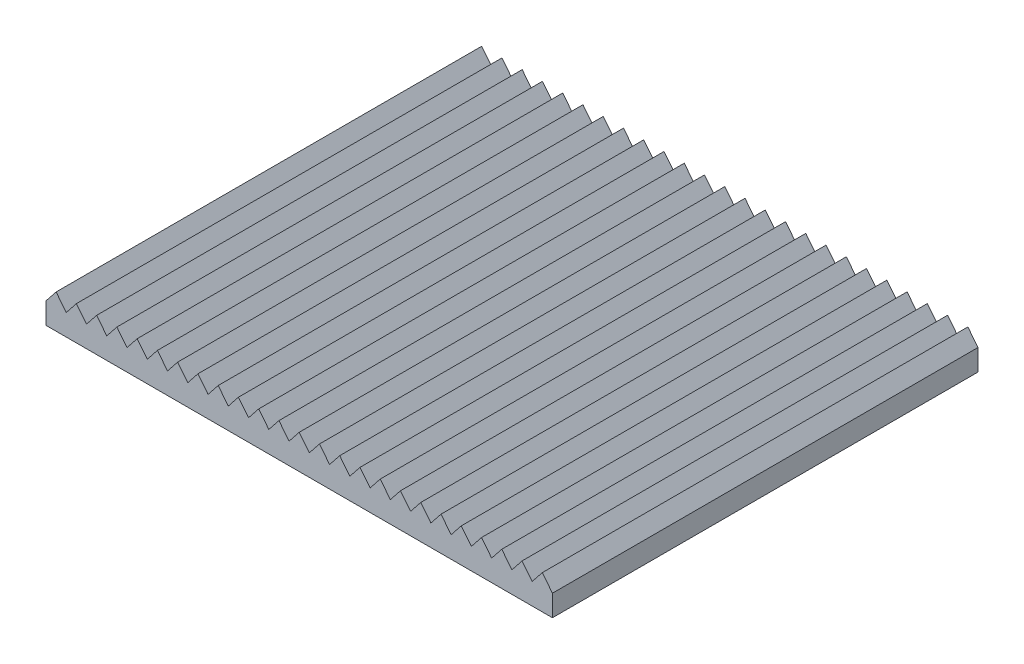
SolidWorks part; units mm, degrees
ref_plane "Front Plane" through (0, 0, 0) normal (0, 0, 1) x (1, 0, 0)
ref_plane "Top Plane" through (0, 0, 0) normal (0, 1, 0) x (1, 0, 0)
ref_plane "Right Plane" through (0, 0, 0) normal (1, 0, 0) x (0, 0, -1)
sketch "Sketch1" plane through (0, 0, 0) normal (0, 1, 0) x (1, 0, 0)
  line L6 (-29.75, 25) -> (29.75, 25)
  line L28 (-29.75, 25) -> (-29.75, -25)
  line L29 (-29.75, -25) -> (29.75, -25)
  line L30 (29.75, 25) -> (29.75, -25)
  line L31 (-29.75, 25) -> (29.75, -25) construction
  line L32 (-29.75, -25) -> (29.75, 25) construction
  circle A1 centre (0, 0) radius 3
  point P0 (0, 0)
  dimension "D3" = 6
  dimension "D1" = 59.5
  dimension "D2" = 50
extrude "Boss-Extrude1" add sketch "Sketch1" along normal blind 1.5
sketch "Sketch2" plane through (0, 0, -25) normal (0, 0, -1) x (-1, 0, 0)
  line L0 (-29.75, 1.5) -> (-29.75, 0) construction
  line L1 (-29.75, 1.5) -> (29.75, 1.5)
  line L2 (-29.75, 1.5) -> (-29.75, 2.5)
  line L4 (29.75, 1.5) -> (29.75, 2.5)
  line L5 (-1.19, 2.5) -> (0, 4)
  line L6 (0, 0.825) -> (0, -0.825) construction
  line L7 (1.19, 2.5) -> (0, 4)
  line L8 (1.19, 2.5) -> (2.38, 4)
  line L9 (3.57, 2.5) -> (2.38, 4)
  line L10 (3.57, 2.5) -> (4.76, 4)
  line L11 (5.95, 2.5) -> (4.76, 4)
  line L12 (5.95, 2.5) -> (7.14, 4)
  line L13 (8.33, 2.5) -> (7.14, 4)
  line L14 (8.33, 2.5) -> (9.52, 4)
  line L15 (10.71, 2.5) -> (9.52, 4)
  line L16 (10.71, 2.5) -> (11.9, 4)
  line L17 (13.09, 2.5) -> (11.9, 4)
  line L18 (13.09, 2.5) -> (14.28, 4)
  line L19 (15.47, 2.5) -> (14.28, 4)
  line L20 (15.47, 2.5) -> (16.66, 4)
  line L21 (17.85, 2.5) -> (16.66, 4)
  line L22 (17.85, 2.5) -> (19.04, 4)
  line L23 (20.23, 2.5) -> (19.04, 4)
  line L24 (20.23, 2.5) -> (21.42, 4)
  line L25 (22.61, 2.5) -> (21.42, 4)
  line L26 (22.61, 2.5) -> (23.8, 4)
  line L27 (24.99, 2.5) -> (23.8, 4)
  line L28 (24.99, 2.5) -> (26.18, 4)
  line L29 (27.37, 2.5) -> (26.18, 4)
  line L30 (27.37, 2.5) -> (28.56, 4)
  line L31 (29.75, 2.5) -> (28.56, 4)
  line L32 (-29.75, 2.5) -> (-28.56, 4)
  line L33 (-27.37, 2.5) -> (-28.56, 4)
  line L34 (-27.37, 2.5) -> (-26.18, 4)
  line L35 (-24.99, 2.5) -> (-26.18, 4)
  line L36 (-24.99, 2.5) -> (-23.8, 4)
  line L37 (-22.61, 2.5) -> (-23.8, 4)
  line L38 (-22.61, 2.5) -> (-21.42, 4)
  line L39 (-20.23, 2.5) -> (-21.42, 4)
  line L40 (-20.23, 2.5) -> (-19.04, 4)
  line L41 (-17.85, 2.5) -> (-19.04, 4)
  line L42 (-17.85, 2.5) -> (-16.66, 4)
  line L43 (-15.47, 2.5) -> (-16.66, 4)
  line L44 (-15.47, 2.5) -> (-14.28, 4)
  line L45 (-13.09, 2.5) -> (-14.28, 4)
  line L46 (-13.09, 2.5) -> (-11.9, 4)
  line L47 (-10.71, 2.5) -> (-11.9, 4)
  line L48 (-10.71, 2.5) -> (-9.52, 4)
  line L49 (-8.33, 2.5) -> (-9.52, 4)
  line L50 (-8.33, 2.5) -> (-7.14, 4)
  line L51 (-5.95, 2.5) -> (-7.14, 4)
  line L52 (-5.95, 2.5) -> (-4.76, 4)
  line L53 (-3.57, 2.5) -> (-4.76, 4)
  line L54 (-3.57, 2.5) -> (-2.38, 4)
  line L55 (-1.19, 2.5) -> (-2.38, 4)
  dimension "D1" = 1
  dimension "D2" = 1.5
  dimension "D3" = 13
extrude "Boss-Extrude2" add sketch "Sketch2" against normal blind 50
sketch "Sketch3" plane through (0, 0, 0) normal (0, -1, 0) x (-1, 0, 0)
  line L0 (0, 2.2) -> (0, -2.2) construction
  line L2 (-1.75, -2.4367) -> (-1.75, -5)
  line L3 (-1.75, -5) -> (1.75, -5)
  line L4 (1.75, -2.4367) -> (1.75, -5)
  arc A0 (1.75, -2.4367) -> (-1.75, -2.4367) centre (0, 0) ccw
  dimension "D2" = 6
  dimension "D1" = 3.5
  dimension "D3" = 5
  dimension "D4" = 1.75
extrude "Cut-Extrude1" cut sketch "Sketch3" against normal blind 2
chamfer "Chamfer1" distance 2 angle 45 1 edges at (0, 0, 5)
